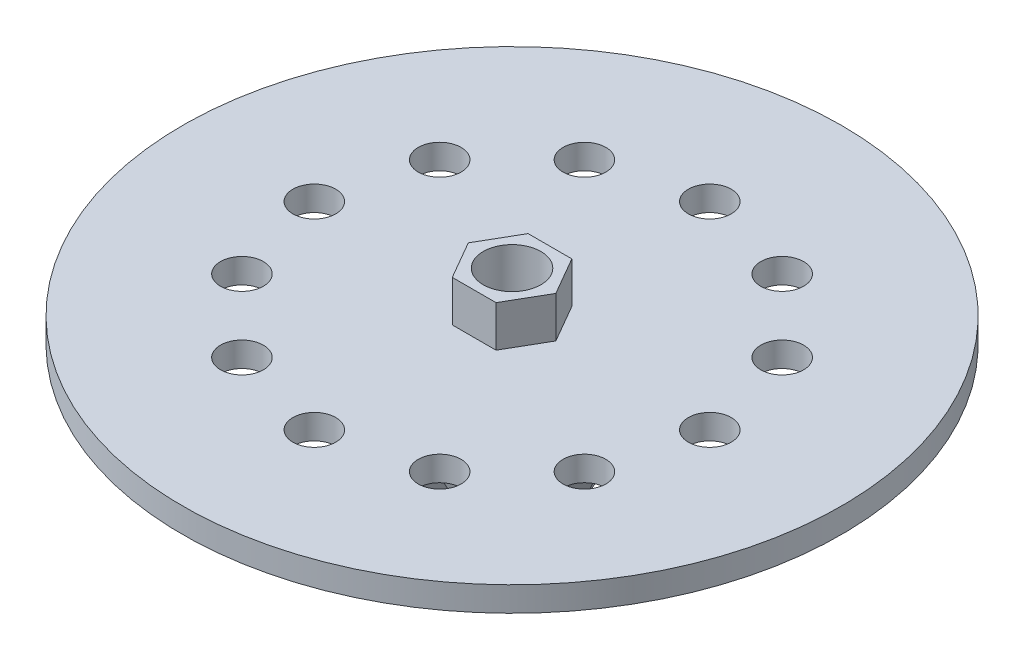
SolidWorks part; units mm, degrees
ref_plane "Front Plane" through (0, 0, 0) normal (0, 0, 1) x (1, 0, 0)
ref_plane "Top Plane" through (0, 0, 0) normal (0, 1, 0) x (1, 0, 0)
ref_plane "Right Plane" through (0, 0, 0) normal (1, 0, 0) x (0, 0, -1)
sketch "Sketch1" plane through (0, 0, 0) normal (0, 1, 0) x (1, 0, 0)
  circle A0 centre (0, 0) radius 50.8
  dimension "D1" = 101.6
extrude "Boss-Extrude1" add sketch "Sketch1" along normal blind 3.81
sketch "Sketch4" plane through (0, 3.81, 0) normal (0, 1, 0) x (1, 0, 0)
  line L0 (-3.3729, 5.842) -> (3.3729, 5.842)
  line L1 (3.3729, 5.842) -> (6.7458, 0)
  line L2 (6.7458, 0) -> (3.3729, -5.842)
  line L3 (3.3729, -5.842) -> (-3.3729, -5.842)
  line L4 (-3.3729, -5.842) -> (-6.7458, 0)
  line L5 (-6.7458, 0) -> (-3.3729, 5.842)
  circle A0 centre (0, 0) radius 4.445
  point P6 (0, 5.842)
  dimension "D3" = 8.89
  dimension "D1" = 120
  dimension "D2" = 11.684
extrude "Boss-Extrude2" add sketch "Sketch4" along normal blind 6.35 contours L5 L4 L3 L2 L1 L0 A0 region at (0, 3.81, -5.6635)
sketch "Sketch5" plane through (0, 3.81, 0) normal (0, 1, 0) x (1, 0, 0)
  circle A0 centre (0, 30.48) radius 3.302
  circle A1 centre (15.24, 26.3965) radius 3.302
  circle A2 centre (26.3965, 15.24) radius 3.302
  circle A3 centre (30.48, 0) radius 3.302
  circle A4 centre (26.3965, -15.24) radius 3.302
  circle A5 centre (15.24, -26.3965) radius 3.302
  circle A6 centre (0, -30.48) radius 3.302
  circle A7 centre (-15.24, -26.3965) radius 3.302
  circle A8 centre (-26.3965, -15.24) radius 3.302
  circle A9 centre (-30.48, 0) radius 3.302
  circle A10 centre (-26.3965, 15.24) radius 3.302
  circle A11 centre (-15.24, 26.3965) radius 3.302
  point P28 (0, 0)
  dimension "D2" = 6.604
  dimension "D1" = 30.48
extrude "Cut-Extrude1" cut sketch "Sketch5" against normal through all
sketch "Sketch6" plane through (0, 0, 0) normal (0, -1, 0) x (1, 0, 0)
  circle A0 centre (0, 0) radius 3.2639
  circle A1 centre (0, 0) radius 9.525
  dimension "D1" = 6.5278
  dimension "D2" = 19.05
extrude "Boss-Extrude3" add sketch "Sketch6" along normal blind 16.51 contours A1 A0 region at (-9.2556, 0, 0)
sketch "Sketch7" plane through (0, 0, 0) normal (0, -1, 0) x (1, 0, 0)
  line L2 (-3.2639, 0) -> (-3.2639, 20.32)
  line L3 (-3.2639, 20.32) -> (3.2639, 20.32)
  line L4 (3.2639, 0) -> (3.2639, 20.32)
  circle A0 centre (0, 0) radius 3.2639 construction
  arc A1 (3.2639, 0) -> (-3.2639, 0) centre (0, 0) ccw
  circle A2 centre (0, 0) radius 3.2639 construction
  dimension "D1" = 20.32
extrude "Boss-Extrude4" add sketch "Sketch7" along normal up to surface (16.51 mm away) up to face at (0, -16.51, -3.2639)
chamfer "Chamfer1" distance 10.16 angle 61 1 edges at (0, -16.51, 20.32) first distance on face at (0, -16.51, -3.2639)
pattern_circular "CirPattern1" count 5 over 360 about axis through (0, -16.51, 0) along (0, 1, 0) of "Boss-Extrude4", "Chamfer1" reverse direction yes
